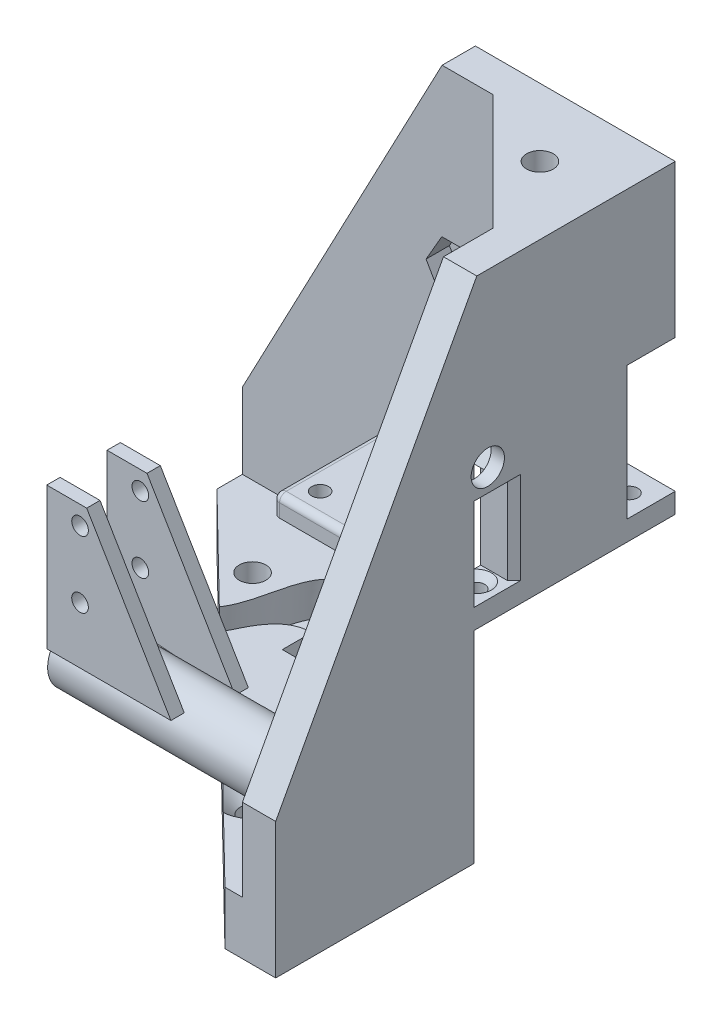
SolidWorks part; units mm, degrees
ref_plane "Front" through (0, 0, 0) normal (0, 0, 1) x (1, 0, 0)
ref_plane "Top" through (0, 0, 0) normal (0, 1, 0) x (1, 0, 0)
ref_plane "Right" through (0, 0, 0) normal (1, 0, 0) x (0, 0, -1)
sketch "Sketch1" plane through (0, 0, 0) normal (0, 1, 0) x (1, 0, 0)
  line L0 (-34.4663, 5.5479) -> (17.9137, -45.6289)
  line L1 (-34.4663, 14.3711) -> (25.5337, 14.3711)
  line L2 (-34.4663, 14.3711) -> (-34.4663, -45.6289)
  line L3 (-34.4663, -45.6289) -> (25.5337, -45.6289)
  line L4 (25.5337, 14.3711) -> (25.5337, -45.6289)
  circle A0 centre (7.6521, -31.0695) radius 2
  circle A1 centre (-20.9229, -2.6469) radius 2
  dimension "D3" = 17.8816
  dimension "D4" = 45.4406
  dimension "D5" = 17.018
  dimension "D6" = 46.4566
  dimension "D7" = 4
  dimension "D8" = 4
  dimension "D1" = 60
  dimension "D2" = 60
extrude "Boss-Extrude1" add sketch "Sketch1" along normal blind 8 contours L4 L1 L2 L0 L3
sketch "Sketch3" plane through (0, 8, 0) normal (0, 1, 0) x (1, 0, 0)
  line L0 (-34.4663, 9.3711) -> (20.5337, 9.3711)
  line L1 (20.5337, 9.3711) -> (20.5337, -45.6289)
  line L5 (25.5337, -45.6289) -> (25.5337, 14.3711)
  line L6 (25.5337, 14.3711) -> (-34.4663, 14.3711)
  line L7 (-34.4663, 14.3711) -> (-34.4663, 5.5479)
  line L8 (-34.4663, 5.5479) -> (17.9137, -45.6289)
  line L9 (17.9137, -45.6289) -> (25.5337, -45.6289)
  line L10 (25.5337, -45.6289) -> (25.5337, 14.3711)
  line L11 (25.5337, 14.3711) -> (-34.4663, 14.3711)
  line L12 (-34.4663, 14.3711) -> (-34.4663, 5.5479)
  line L13 (-34.4663, 5.5479) -> (17.9137, -45.6289)
  line L14 (17.9137, -45.6289) -> (25.5337, -45.6289)
  line M8 (25.5337, -45.6289) -> (25.5337, 14.3711)
  line M9 (25.5337, 14.3711) -> (-34.4663, 14.3711)
  line M10 (-34.4663, 14.3711) -> (-34.4663, 5.5479)
  line M12 (17.9137, -45.6289) -> (25.5337, -45.6289)
  dimension "D2" = 5
  dimension "D3" = 5
  dimension "D1" = 0
extrude "Boss-Extrude3" add sketch "Sketch3" along normal blind 76.2 from surface at -8 contours L0 L1 M12 M8 M9 M10 | L11 L12 L13 L14 L10
sketch "Sketch4" plane through (0, 8, 0) normal (0, 1, 0) x (1, 0, 0)
  line L1 (25.5337, 14.3711) -> (-3.6763, 14.3711)
  line L2 (25.5337, 14.3711) -> (25.5337, -14.8389)
  line L3 (25.5337, -14.8389) -> (-3.6763, -14.8389)
  line L4 (-3.6763, 14.3711) -> (-3.6763, -14.8389)
  line L5 (20.5337, -45.6289) -> (20.5337, 9.3711)
  line L6 (-34.4663, 9.3711) -> (20.5337, 9.3711)
  line L7 (20.5337, 9.3711) -> (20.5337, -45.6289)
  line L8 (20.5337, -45.6289) -> (25.5337, -45.6289)
  line L9 (25.5337, -45.6289) -> (25.5337, 14.3711)
  line L10 (25.5337, 14.3711) -> (-34.4663, 14.3711)
  line L11 (-34.4663, 14.3711) -> (-34.4663, 9.3711)
  line L12 (-34.4663, 9.3711) -> (20.5337, 9.3711)
  line L13 (20.5337, 9.3711) -> (20.5337, -45.6289)
  line L14 (20.5337, -45.6289) -> (25.5337, -45.6289)
  line L15 (25.5337, -45.6289) -> (25.5337, 14.3711)
  line L16 (25.5337, 14.3711) -> (-34.4663, 14.3711)
  line L17 (-34.4663, 14.3711) -> (-34.4663, 9.3711)
  line L18 (20.5337, 9.3711) -> (-34.4663, 9.3711)
  line L19 (-34.4663, 9.3711) -> (-34.4663, 5.5479)
  line L20 (-34.4663, 5.5479) -> (17.9137, -45.6289)
  line L21 (17.9137, -45.6289) -> (20.5337, -45.6289)
  line L22 (20.5337, -45.6289) -> (20.5337, 9.3711)
  line L23 (20.5337, 9.3711) -> (-34.4663, 9.3711)
  line L24 (-34.4663, 9.3711) -> (-34.4663, 5.5479)
  line L25 (-34.4663, 5.5479) -> (17.9137, -45.6289)
  line L26 (17.9137, -45.6289) -> (20.5337, -45.6289)
  dimension "D3" = 29.21
  dimension "D4" = 29.21
  dimension "D1" = 0
  dimension "D2" = 0
extrude "Cut-Extrude1" cut sketch "Sketch4" against normal up to next and the other way blind 22.3 contours L1 L4 L3 L2
sketch "Sketch5" plane through (0, 30.3, 0) normal (0, -1, 0) x (1, 0, 0)
  line L0 (-3.6763, 14.8389) -> (25.5337, 14.8389) construction
  line L1 (-3.6763, 14.8389) -> (-3.6763, -14.3711) construction
  line L2 (25.5337, -14.3711) -> (-3.6763, -14.3711) construction
  line L3 (25.5337, -14.3711) -> (25.5337, 14.8389) construction
  line L4 (-3.6763, 14.8389) -> (25.5337, 14.8389)
  line L5 (-3.6763, 14.8389) -> (-3.6763, -14.3711)
  line L6 (25.5337, -14.3711) -> (-3.6763, -14.3711)
  line L7 (25.5337, -14.3711) -> (25.5337, 14.8389)
  line L9 (21.8237, 12.3389) -> (-1.1763, 12.3389)
  line L10 (21.8237, 12.3389) -> (21.8237, -10.6611)
  line L11 (21.8237, -10.6611) -> (-1.1763, -10.6611)
  line L12 (-1.1763, 12.3389) -> (-1.1763, -10.6611)
  line L13 (25.5337, -14.3711) -> (19.3237, -14.3711)
  line L14 (25.5337, -14.3711) -> (25.5337, -8.1611)
  line L15 (25.5337, -8.1611) -> (19.3237, -8.1611)
  line L16 (19.3237, -14.3711) -> (19.3237, -8.1611)
  line L17 (-3.6763, -14.3711) -> (1.3237, -14.3711)
  line L18 (-3.6763, -14.3711) -> (-3.6763, -8.1611)
  line L19 (-3.6763, -8.1611) -> (1.3237, -8.1611)
  line L20 (1.3237, -14.3711) -> (1.3237, -8.1611)
  line L21 (25.5337, 14.8389) -> (19.3237, 14.8389)
  line L22 (25.5337, 14.8389) -> (25.5337, 9.8389)
  line L23 (25.5337, 9.8389) -> (19.3237, 9.8389)
  line L24 (19.3237, 14.8389) -> (19.3237, 9.8389)
  line M10 (20.5337, -9.3711) -> (-3.6763, -9.3711)
  line M11 (-3.6763, -9.3711) -> (-3.6763, -14.3711)
  line M12 (-3.6763, -14.3711) -> (25.5337, -14.3711)
  line M13 (25.5337, -14.3711) -> (25.5337, 14.8389)
  line M15 (20.5337, 14.8389) -> (20.5337, -9.3711)
  dimension "D1" = 23
  dimension "D2" = 23
  dimension "D3" = 2.5
  dimension "D4" = 2.5
  dimension "D5" = 2.5
  dimension "D6" = 2.5
  dimension "D7" = 2.5
  dimension "D8" = 2.5
  dimension "D9" = 2.5
extrude "Cut-Extrude2" cut sketch "Sketch5" against normal blind 20 from offset 3 contours L20 L11 L12 M12 M10 M11 | L11 L20 L12 M10 | L20 L19 L12 M10 | L16 L6 L15 L10 L11 M13 | L16 L11 L10 L15 M15 M10 | L16 L15 M10 M15 offset against normal yes
sketch "Sketch6" plane through (0, 30.3, 0) normal (0, -1, 0) x (1, 0, 0)
  line L1 (-3.6763, 14.8389) -> (25.5337, 14.8389) construction
  line L2 (-3.6763, 14.8389) -> (-3.6763, -14.3711) construction
  circle A0 centre (22.3237, 12.2889) radius 1.25
  circle A2 centre (22.3237, -10.7111) radius 1.25
  circle A3 centre (-0.6763, -10.7111) radius 1.25
  dimension "D1" = 2.55
  dimension "D2" = 26
  dimension "D3" = 2.5
  dimension "D4" = 23
  dimension "D5" = 23
extrude "Cut-Extrude3" cut sketch "Sketch6" against normal up to next
chamfer "Chamfer1" distance 1 angle 45 8 edges at (-3.6763, 15.15, -14.3711) (1.3237, 43.3, -14.3711) (19.3237, 43.3, -14.3711) (25.5337, 43.3, -8.1611) (25.5337, 43.3, 9.8389) (25.5337, 15.15, 14.8389) (-3.6763, 43.3, -14.3711) (25.5337, 43.3, 14.8389)
sketch "Sketch7" plane through (0, 0, -9.3711) normal (0, 0, 1) x (1, 0, 0)
  line L0 (-4.4781, 76.2) -> (-34.4663, 19.3455)
  line L1 (-34.4663, 76.2) -> (20.5337, 76.2) construction
  line L2 (-34.4663, 76.2) -> (-34.4663, 8) construction
  line L3 (-34.4663, 19.3455) -> (-34.4663, 76.2)
  line L4 (-34.4663, 76.2) -> (-4.4781, 76.2)
extrude "Cut-Extrude4" cut sketch "Sketch7" against normal up to next
sketch "Sketch8" plane through (20.5337, 0, 0) normal (-1, 0, 0) x (0, 0, 1)
  line L0 (15.4321, 76.2) -> (45.6289, 20.3609)
  line L1 (-9.3711, 76.2) -> (45.6289, 76.2) construction
  line L2 (45.6289, 76.2) -> (45.6289, 8) construction
  line L3 (45.6289, 20.3609) -> (45.6289, 76.2)
  line L4 (45.6289, 76.2) -> (15.4321, 76.2)
  line L5 (-5.5479, 8) -> (45.6289, 8) construction
  circle A0 centre (34.7196, 16.9535) radius 2.6
  line M15 (45.6289, 8) -> (45.6289, 76.2)
  line M16 (45.6289, 76.2) -> (-9.3711, 76.2)
  dimension "D1" = 10.9093
  dimension "D3" = 5.2
  dimension "D2" = 8.9535
extrude "Cut-Extrude5" cut sketch "Sketch8" against normal up to next contours L0 M16 M15
sketch "Sketch9" plane through (0, 30.3, 0) normal (0, -1, 0) x (1, 0, 0)
  line L0 (-4.6763, -14.3711) -> (-4.6763, 15.8389)
  line L1 (-4.6763, 15.8389) -> (25.5337, 15.8389)
  line L2 (25.5337, -14.3711) -> (-13.9259, 25.0885) construction
  line L3 (25.5337, -14.3711) -> (-4.6763, -14.3711) construction
  line L4 (-4.6763, -14.3711) -> (0.9008, -14.3711)
  line L5 (25.5337, 10.2619) -> (25.5337, 15.8389)
  line L6 (25.5337, -14.3711) -> (25.5337, 15.8389) construction
  arc A0 (0.9008, -14.3711) -> (1.8042, 9.3584) centre (25.0313, -3.4078) cw
  arc A1 (25.5337, 10.2619) -> (1.8042, 9.3584) centre (14.5705, -13.8686) ccw
  circle A2 centre (-0.6763, -10.7111) radius 1.25 construction
  circle A3 centre (22.3237, 12.2889) radius 1.25 construction
  circle A4 centre (-0.6763, -10.7111) radius 1.25
  circle A5 centre (22.3237, 12.2889) radius 1.25
  circle A6 centre (-1.1263, 12.2889) radius 1.25
  circle M8 centre (22.3237, 12.2889) radius 1.25
  circle M9 centre (-0.6763, -10.7111) radius 1.25
  line M11 (20.5337, -9.3711) -> (-3.6763, -9.3711)
  line M12 (-3.6763, -9.3711) -> (-3.6763, -13.3711)
  line M13 (-3.6763, -13.3711) -> (-4.6763, -14.3711)
  line M14 (-4.6763, -14.3711) -> (25.5337, -14.3711)
  line M15 (25.5337, -14.3711) -> (25.5337, 15.8389)
  line M16 (25.5337, 15.8389) -> (24.5337, 14.8389)
  line M17 (24.5337, 14.8389) -> (20.5337, 14.8389)
  line M18 (20.5337, 14.8389) -> (20.5337, -9.3711)
  dimension "D1" = 5.5771
extrude "Boss-Extrude4" add sketch "Sketch9" against normal blind 3 contours A0 M14 M9 M11 M12 M13 | A1 M15 M16 M17 M18 M8 | L2 A1 L1 M18 M17 M16 | A0 L2 L0 M13 M12 M11
fillet "Fillet2" radius 1 4 edges at (7.9287, 33.3, 15.8389) (-4.6763, 33.3, 3.2339) (-4.6763, 31.8, 15.8389) (-0.7934, 31.8, -9.3711)
sketch "Sketch10" plane through (0, 30.3, 0) normal (0, -1, 0) x (1, 0, 0)
  line L0 (22.3237, 12.2889) -> (-0.6763, -10.7111) construction
  circle A0 centre (10.8237, 0.7889) radius 11.5
extrude "Cut-Extrude6" cut sketch "Sketch10" against normal blind 3
sketch "Sketch12" plane through (20.5337, 0, 0) normal (-1, 0, 0) x (0, 0, 1)
  line L0 (45.6289, 20.3609) -> (45.6289, 8) construction
  line L1 (-5.5479, 8) -> (45.6289, 8) construction
  circle A0 centre (34.7189, 16.95) radius 2.6
  circle A1 centre (34.7189, 16.95) radius 4.6
  dimension "D1" = 10.91
  dimension "D2" = 8.95
  dimension "D3" = 5.2
  dimension "D4" = 2
extrude "Boss-Extrude5" add sketch "Sketch12" along normal blind 35.56
fillet "Fillet3" radius 1 1 edges at (-15.0263, 16.95, 37.3189)
chamfer "Chamfer2" distance 1 angle 45 2 edges at (22.3237, 33.3, 13.5389) (-0.6763, 33.3, -11.9611)
sketch "Sketch14" plane through (25.5337, 0, 0) normal (1, 0, 0) x (0, 0, -1)
  line L1 (-19.4539, 57.4719) -> (-7.0581, 57.4719)
  line L2 (-19.4539, 57.4719) -> (-19.4539, 47.1223)
  line L3 (-19.4539, 47.1223) -> (-7.0581, 47.1223)
  line L4 (-7.0581, 57.4719) -> (-7.0581, 47.1223)
extrude "Boss-Extrude6" add sketch "Sketch14" against normal up to surface (5 mm away) up to face at (20.5337, 16.95, 30.1189)
sketch "Sketch13" plane through (25.5337, 0, 0) normal (1, 0, 0) x (0, 0, -1)
  line L0 (55, 0) -> (-55, 0) construction
  line L2 (14.3711, 76.2) -> (14.3711, 53.3) construction
  circle A0 centre (-13.7829, 50.506) radius 2.5
  dimension "D1" = 50.506
  dimension "D2" = 5
  dimension "D3" = 28.154
extrude "Cut-Extrude7" cut sketch "Sketch13" against normal blind 20
sketch "Sketch15" plane through (20.5337, 0, 0) normal (-1, 0, 0) x (0, 0, 1)
  line L1 (16.1501, 46.406) -> (18.5172, 50.506)
  line L2 (18.5172, 50.506) -> (16.1501, 54.606)
  line L3 (16.1501, 54.606) -> (11.4158, 54.606)
  line L4 (11.4158, 54.606) -> (9.0487, 50.506)
  line L5 (9.0487, 50.506) -> (11.4158, 46.406)
  line L6 (11.4158, 46.406) -> (16.1501, 46.406)
  circle A0 centre (13.7829, 50.506) radius 4.1 construction
  dimension "D1" = 8.2
extrude "Cut-Extrude8" cut sketch "Sketch15" against normal blind 3
sketch "Sketch16" plane through (-15.0263, 0, 0) normal (-1, 0, 0) x (0, 0, 1)
  line L1 (29.2053, 20.25) -> (29.2053, 41.55)
  line L2 (29.2053, 41.55) -> (31.2053, 41.55)
  line L3 (31.2053, 41.55) -> (31.2053, 21.55)
  line L4 (31.2053, 21.55) -> (34.7321, 21.55)
  line L6 (29.2053, 20.25) -> (40.259, 20.25)
  line L7 (34.7321, 20.25) -> (34.7321, 21.55)
  line L8 (40.259, 20.25) -> (40.259, 41.55)
  line L9 (40.259, 41.55) -> (38.259, 41.55)
  line L10 (38.259, 41.55) -> (38.259, 21.55)
  line L11 (38.259, 21.55) -> (34.7321, 21.55)
  circle A2 centre (34.7189, 16.95) radius 4.6 construction
  point P0 (32.9687, 21.55)
  circle M14 centre (34.7189, 16.95) radius 4.6
  dimension "D1" = 1.3
  dimension "D2" = 21.3
  dimension "D3" = 2
extrude "Boss-Extrude7" add sketch "Sketch16" against normal blind 6 from offset 0.81 contours L1 L6 L4 L3 L2 M14 | L10 L11 L7 L6 L8 L9 M14 offset against normal yes
sketch "Sketch17" plane through (0, 0, 40.259) normal (0, 0, 1) x (1, 0, 0)
  line L0 (-8.2163, 41.55) -> (4.4337, 20.25)
  line L1 (4.4337, 20.25) -> (-8.2163, 20.25)
  line L2 (-8.2163, 20.25) -> (-8.2163, 41.55)
  dimension "D1" = 12.65
extrude "Boss-Extrude8" add sketch "Sketch17" against normal up to surface (2 mm away) up to face at (-11.2163, 31.55, 38.259)
sketch "Sketch18" plane through (0, 0, 31.2053) normal (0, 0, 1) x (1, 0, 0)
  line L0 (-8.2163, 41.55) -> (5.0053, 19.2874)
  line L1 (4.4337, 20.25) -> (-8.2163, 41.55) construction
  line L2 (5.0053, 19.2874) -> (-8.2163, 20.25)
  line L3 (4.4337, 20.25) -> (-14.2163, 20.25) construction
  line L4 (-8.2163, 20.25) -> (-8.2163, 41.55)
  line M3 (-8.2163, 21.55) -> (-8.2163, 41.55)
extrude "Boss-Extrude9" add sketch "Sketch18" against normal up to surface (2 mm away) contours L4 L2 L0 M3 up to face at (-11.2163, 30.9, 29.2053)
sketch "Sketch19" plane through (0, 0, 40.259) normal (0, 0, 1) x (1, 0, 0)
  line L0 (-14.2163, 20.25) -> (-14.2163, 41.55) construction
  line L2 (4.4337, 20.25) -> (-14.2163, 20.25) construction
  circle A0 centre (-9.2163, 38.75) radius 1.25
  circle A1 centre (-9.2163, 28.75) radius 1.25
  dimension "D1" = 2.5
  dimension "D2" = 10
  dimension "D3" = 5
  dimension "D4" = 18.5
extrude "Cut-Extrude9" cut sketch "Sketch19" against normal up to surface (11.0537 mm away) up to face at (-7.972, 28.5775, 29.2053)
sketch "Sketch20" plane through (0, 8, 0) normal (0, 1, 0) x (1, 0, 0)
  line L0 (-3.6763, -14.8389) -> (-3.6763, 9.3711) construction
  line L1 (-3.6763, 7.0764) -> (-8.6763, 7.0764)
  line L2 (-3.6763, 7.0764) -> (-3.6763, -10.4236)
  line L3 (-3.6763, -10.4236) -> (-8.6763, -10.4236)
  line L4 (-8.6763, 7.0764) -> (-8.6763, -10.4236)
  line L5 (-34.4663, 5.5479) -> (17.9137, -45.6289) construction
  line L6 (-18.9661, -9.5963) -> (-15.6566, -12.8298)
  line L7 (-8.6763, 4.0206) -> (-8.6763, -5.9794)
  spline S0 degree 3 poles (-8.6763, 4.0206) (-18.0245, 4.4014) (-15.5798, -4.5075) (-18.9661, -9.5963) knots 0 0 0 0 1 1 1 1
  spline S1 degree 3 poles (-8.6763, -5.9794) (-12.8043, -6.0655) (-14.1575, -9.8395) (-15.6566, -12.8298) knots 0 0 0 0 1 1 1 1
  dimension "D1" = 5
  dimension "D2" = 17.5
  dimension "D3" = 10
extrude "Cut-Extrude10" cut sketch "Sketch20" against normal up to surface (8 mm away) contours L4 L3 L2 L1 | S0 L6 S1 L7 up to face at (-20.9229, 0, 4.6469)
sketch "Sketch21" plane through (0, 0, 0) normal (0, -1, 0) x (1, 0, 0)
  line L0 (-15.6566, 12.8298) -> (-18.9661, 9.5963)
  line L1 (-12.3568, -3.5335) -> (-9.8317, 6.1108)
  line L7 (-3.6763, -13.3711) -> (-3.6763, -7.0764)
  line L8 (-8.6763, 10.4236) -> (-3.6763, 10.4236)
  line L9 (-3.6763, 10.4236) -> (-3.6763, 14.8389)
  line L10 (-3.6763, 14.8389) -> (24.5337, 14.8389)
  line L11 (24.5337, 14.8389) -> (25.5337, 15.8389)
  line L12 (25.5337, 15.8389) -> (25.5337, 45.6289)
  line L13 (25.5337, 45.6289) -> (17.9137, 45.6289)
  line L14 (17.9137, 45.6289) -> (-15.6566, 12.8298)
  line L15 (-8.6763, 5.9794) -> (-8.6763, 10.4236)
  line L17 (-3.6763, 10.4236) -> (-3.6763, 14.8389)
  line L18 (-3.6763, 14.8389) -> (24.5337, 14.8389)
  line L19 (24.5337, 14.8389) -> (25.5337, 15.8389)
  line L20 (25.5337, 15.8389) -> (25.5337, 45.6289)
  line L21 (25.5337, 45.6289) -> (17.9137, 45.6289)
  line L24 (-3.6763, -7.0764) -> (-8.6763, -7.0764)
  line L25 (-8.6763, -7.0764) -> (-8.6763, -4.0206)
  line L26 (-18.9661, 9.5963) -> (-34.4663, -5.5479)
  line L27 (-34.4663, -5.5479) -> (-34.4663, -14.3711)
  line L28 (-34.4663, -14.3711) -> (-4.6763, -14.3711)
  line L29 (-4.6763, -14.3711) -> (-3.6763, -13.3711)
  line L30 (-3.6763, -13.3711) -> (-3.6763, -7.0764)
  line L31 (-3.6763, -7.0764) -> (-8.6763, -7.0764)
  line L34 (-34.4663, -5.5479) -> (-34.4663, -14.3711)
  line L35 (-34.4663, -14.3711) -> (-4.6763, -14.3711)
  line L36 (-4.6763, -14.3711) -> (-3.6763, -13.3711)
  spline S1 degree 3 poles (-1664.0906, -2493.3295) (1618.3693, 2595.8642) (-1683.0086, -2548.6215) (1737.6447, 2444.2179) knots -8.15267 -8.15267 -8.15267 -8.15267 8.424766 8.424766 8.424766 8.424766 only from (-15.6566, 12.8298) to (-8.6763, 5.9794)
  spline S2 degree 3 poles (-15.6566, 12.8298) (-14.307, 10.1377) (-13.0757, 6.8106) (-9.8317, 6.1108) knots 0 0 0 0 0.900249 0.900249 0.900249 0.900249
  spline S3 degree 3 poles (2425.1382, 1749.2025) (-2440.44, -1850.276) (2418.1934, 1839.2449) (-2493.8825, -1684.1528) knots -4.489563 -4.489563 -4.489563 -4.489563 5.852519 5.852519 5.852519 5.852519 only from (-8.6763, -4.0206) to (-18.9661, 9.5963)
  spline S4 degree 3 poles (-12.3568, -3.5335) (-17.387, -1.6237) (-16.1267, 5.3293) (-18.9661, 9.5963) knots 0.161488 0.161488 0.161488 0.161488 1 1 1 1
  spline M28 degree 3 poles (-8.6763, 5.9794) (-12.8043, 6.0655) (-14.1575, 9.8395) (-15.6566, 12.8298) knots 0 0 0 0 1 1 1 1
  dimension "D1" = 0
  dimension "D2" = 0
extrude "Boss-Extrude10" add sketch "Sketch21" against normal blind 3 contours S4 L1 L0 M28
sketch "Sketch22" plane through (0, 0, 0) normal (0, -1, 0) x (1, 0, 0)
  line L0 (5.7693, 31.7442) -> (9.5349, 31.7442)
  circle A0 centre (7.6521, 31.0695) radius 2 construction
  arc A1 (5.7693, 31.7442) -> (9.5349, 31.7442) centre (7.6521, 31.0695) ccw
  point P2 (0, 0)
  point P5 (0, 0)
  point P6 (7.6521, 31.0695)
extrude "Cut-Extrude11" cut sketch "Sketch22" against normal through all
chamfer "Chamfer3" distance 3 angle 45 1 edges at (7.6521, 8, 33.0695)
sketch "Sketch23" plane through (0, 0, -14.3711) normal (0, 0, -1) x (-1, 0, 0)
  line L0 (-25.5337, 76.2) -> (-25.5337, 53.3) construction
  line L1 (-4.5242, 54.5299) -> (7.2145, 54.5299)
  line L2 (-4.5242, 54.5299) -> (-4.5242, 46.3385)
  line L3 (-4.5242, 46.3385) -> (7.2145, 46.3385)
  line L4 (7.2145, 54.5299) -> (7.2145, 46.3385)
  line L5 (-25.5337, 76.2) -> (4.4781, 76.2) construction
  circle A0 centre (2.1523, 49.784) radius 2.5
  dimension "D1" = 27.686
  dimension "D2" = 5
  dimension "D3" = 26.416
extrude "Boss-Extrude11" add sketch "Sketch23" against normal up to surface (5 mm away) up to face at (2.9486, 36.7201, -9.3711)
sketch "Sketch25" plane through (0, 0, -14.3711) normal (0, 0, -1) x (-1, 0, 0)
  circle A0 centre (2.1523, 49.784) radius 2.5 construction
  circle A1 centre (2.1523, 49.784) radius 2.5
extrude "Cut-Extrude12" cut sketch "Sketch25" against normal through all
sketch "Sketch26" plane through (0, 0, -9.3711) normal (0, 0, 1) x (1, 0, 0)
  line L1 (0.2148, 45.684) -> (2.582, 49.784)
  line L2 (2.582, 49.784) -> (0.2148, 53.884)
  line L3 (0.2148, 53.884) -> (-4.5195, 53.884)
  line L4 (-4.5195, 53.884) -> (-6.8866, 49.784)
  line L5 (-6.8866, 49.784) -> (-4.5195, 45.684)
  line L6 (-4.5195, 45.684) -> (0.2148, 45.684)
  circle A0 centre (-2.1523, 49.784) radius 2.5 construction
  circle A1 centre (-2.1523, 49.784) radius 2.5
  circle A2 centre (-2.1523, 49.784) radius 4.1 construction
  dimension "D1" = 8.2
extrude "Cut-Extrude13" cut sketch "Sketch26" against normal blind 3.5
sketch "Sketch27" plane through (0, 76.2, 0) normal (0, 1, 0) x (1, 0, 0)
  line L0 (-1.8005, 14.3711) -> (25.5337, -12.9631)
  line L1 (25.5337, 14.3711) -> (-4.4781, 14.3711) construction
  line L2 (25.5337, -15.4321) -> (25.5337, 14.3711) construction
  line L3 (25.5337, -12.9631) -> (25.5337, 14.3711)
  line L4 (25.5337, 14.3711) -> (-1.8005, 14.3711)
  line L5 (25.5337, 14.3711) -> (11.8666, 0.704) construction
  circle A0 centre (15.3737, 4.2111) radius 2
  dimension "D1" = 4
  dimension "D2" = 10.16
extrude "Boss-Extrude12" add sketch "Sketch27" against normal blind 7
sketch "Sketch29" plane through (0, 69.2, 0) normal (0, -1, 0) x (1, 0, 0)
  line L1 (17.3944, -0.7111) -> (13.353, -0.7111)
  line L2 (13.353, -0.7111) -> (11.3322, -4.2111)
  line L3 (11.3322, -4.2111) -> (13.353, -7.7111)
  line L4 (13.353, -7.7111) -> (17.3944, -7.7111)
  line L5 (17.3944, -7.7111) -> (19.4151, -4.2111)
  line L6 (19.4151, -4.2111) -> (17.3944, -0.7111)
  circle A0 centre (15.3737, -4.2111) radius 2 construction
  circle A1 centre (15.3737, -4.2111) radius 2
  circle A2 centre (15.3737, -4.2111) radius 3.5 construction
  dimension "D1" = 7
extrude "Cut-Extrude14" cut sketch "Sketch29" against normal blind 3.5
